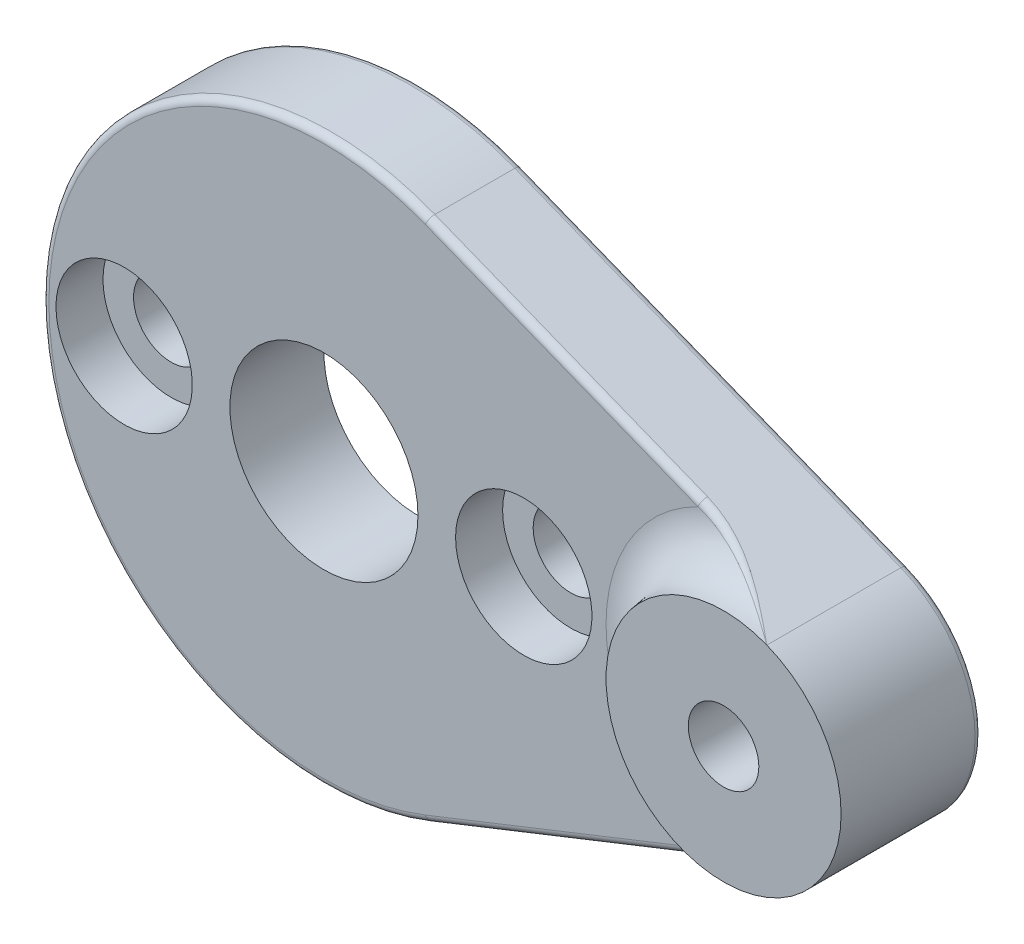
SolidWorks part; units mm, degrees
material "ABS"
ref_plane "Front" through (0, 0, 0) normal (0, 0, 1) x (1, 0, 0)
ref_plane "Top" through (0, 0, 0) normal (0, 1, 0) x (1, 0, 0)
ref_plane "Right" through (0, 0, 0) normal (1, 0, 0) x (0, 0, -1)
sketch "Esquisse1" plane through (0, 0, 0) normal (0, 0, 1) x (1, 0, 0)
  line L0 (4.4211, 11.1559) -> (20.8421, 4.6483)
  line L1 (20.8421, -4.6483) -> (4.4211, -11.1559)
  line L2 (0, -50) -> (0, 50) construction
  circle A0 centre (0, 0) radius 4
  circle A1 centre (19, 0) radius 1.5
  arc A2 (20.8421, 4.6483) -> (20.8421, -4.6483) centre (19, 0) cw
  arc A3 (4.4211, -11.1559) -> (4.4211, 11.1559) centre (0, 0) cw
  circle A4 centre (-8.5, 0) radius 1.6
  circle A5 centre (8.5, 0) radius 1.6
  dimension "D1" = 3
  dimension "D2" = 8
  dimension "D3" = 19
  dimension "D4" = 5
  dimension "D5" = 12
  dimension "D6" = 3.2
  dimension "D7" = 17
extrude "Boss.-Extru.1" add sketch "Esquisse1" along normal blind 4
sketch "Esquisse3" plane through (0, 0, 4) normal (0, 0, 1) x (1, 0, 0)
  circle A0 centre (19, 0) radius 5
  circle A1 centre (19, 0) radius 1.5 construction
  circle A2 centre (19, 0) radius 1.5
  arc A3 (20.8421, -4.6483) -> (20.8421, 4.6483) centre (19, 0) ccw construction
extrude "Boss.-Extru.2" add sketch "Esquisse3" along normal blind 2
sketch "Esquisse4" plane through (0, 0, 0) normal (0, 0, -1) x (-1, 0, 0)
  line L1 (-16.25, -1.5877) -> (-16.25, 1.5877)
  line L2 (-16.25, 1.5877) -> (-19, 3.1754)
  line L3 (-19, 3.1754) -> (-21.75, 1.5877)
  line L4 (-21.75, 1.5877) -> (-21.75, -1.5877)
  line L5 (-21.75, -1.5877) -> (-19, -3.1754)
  line L6 (-19, -3.1754) -> (-16.25, -1.5877)
  circle A1 centre (-19, 0) radius 2.75 construction
  dimension "D1" = 5.5
extrude "Enlèv. mat.-Extru.2" cut sketch "Esquisse4" against normal blind 3
fillet "Congé1" radius 2 1 edges at (14, 0, 4)
fillet "Congé2" radius 0.3 9 edges at (-12, 0, 0) (12.6316, 7.9021, 0) (24, 0, 0) (17.7531, 5.8725, 4.266) (10.3544, 8.8045, 4) (-12, 0, 4) (17.7531, -5.8725, 4.266) (12.6316, -7.9021, 0) (10.3544, -8.8045, 4)
sketch "Esquisse2" plane through (0, 0, 4) normal (0, 0, 1) x (1, 0, 0)
  circle A0 centre (-8.5, 0) radius 2.9
  circle A1 centre (8.5, 0) radius 2.9
  dimension "D1" = 5.8
extrude "Enlèv. mat.-Extru.1" cut sketch "Esquisse2" against normal offset from surface 2 and the other way blind 5 up to face at (9.2605, 0, 0)
